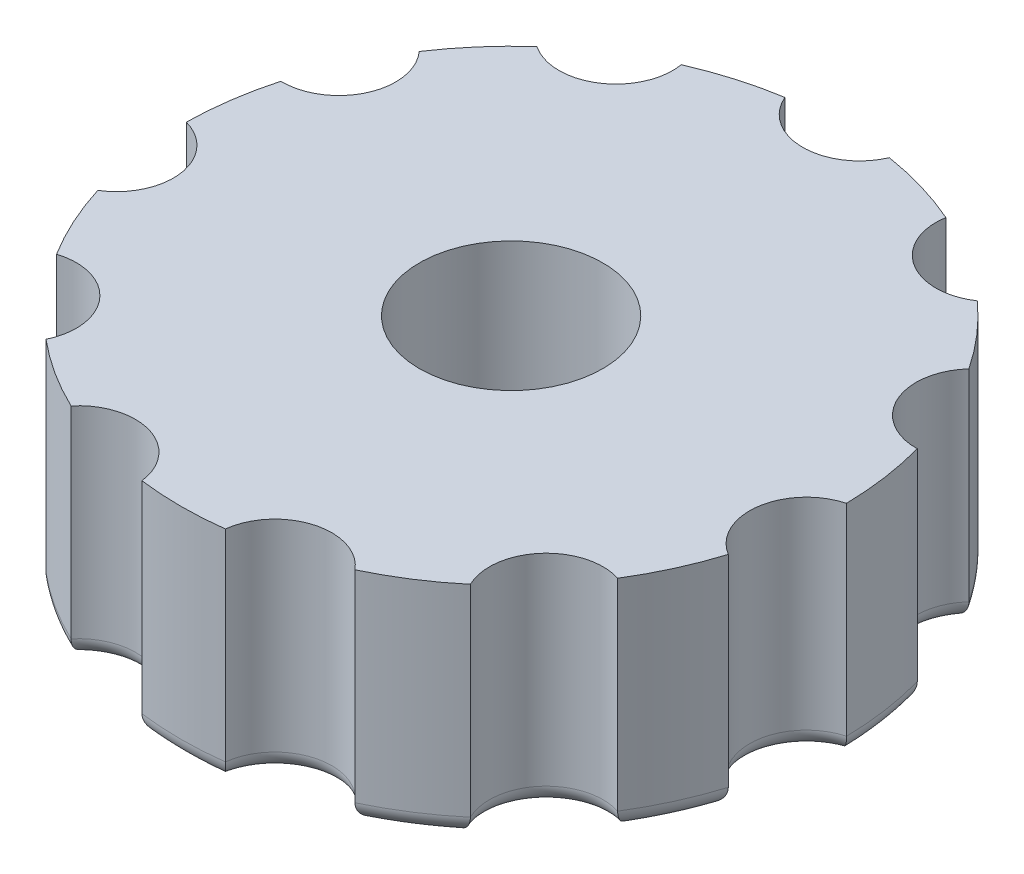
SolidWorks part; units mm, degrees
ref_plane "Front Plane" through (0, 0, 0) normal (0, 0, 1) x (1, 0, 0)
ref_plane "Top Plane" through (0, 0, 0) normal (0, 1, 0) x (1, 0, 0)
ref_plane "Right Plane" through (0, 0, 0) normal (1, 0, 0) x (0, 0, -1)
sketch "Sketch1" plane through (0, 0, 0) normal (0, 1, 0) x (1, 0, 0)
  line L0 (0, 9.5) -> (0, 9) construction
  circle A0 centre (0, 0) radius 9
  circle A1 centre (0, 0) radius 2.5
  circle A2 centre (0, 9.5) radius 1.55
  dimension "D1" = 18
  dimension "D2" = 5
  dimension "D3" = 3.1
  dimension "D4" = 0.5
extrude "Boss-Extrude1" add sketch "Sketch1" along normal blind 6 contours A2 A0 A1 | A0 A2 region at (-5.6744, 0, 6.6557) region at (0, 0, -8.5437)
extrude "Boss-Extrude2" add sketch "Sketch1<3>" along normal blind 2 contours A1
sketch "Sketch1<3>" plane through (0, 0, 0) normal (0, 1, 0) x (1, 0, 0) same geometry as "Sketch1"
ref_axis "Axis1" through (0, 0, 0) along (0, 1, 0)
extrude "Cut-Extrude1" cut sketch "Sketch1<4>" along normal through all contours A2
sketch "Sketch1<4>" plane through (0, 0, 0) normal (0, 1, 0) x (1, 0, 0) same geometry as "Sketch1"
pattern_circular "CirPattern1" count 11 over 360 about axis through (0, 0, 0) along (0, 1, 0) of "Cut-Extrude1"
fillet "Fillet1" radius 0.5 22 edges at (-8.9084, 0, -1.2808) (-7.8691, 0, 1.1314) (-8.1867, 0, 3.7387) (-6.0082, 0, 5.2061) (-4.8658, 0, 7.5713) (-2.2398, 0, 7.628) (0, 0, 9) (2.2398, 0, 7.628) (4.8658, 0, 7.5713) (6.0082, 0, 5.2061) (8.1867, 0, 3.7387) (0, 0, -7.95) (-2.5356, 0, -8.6354) (-4.2981, 0, -6.688) (-6.8017, 0, -5.8937) (-7.2316, 0, -3.3025) (7.8691, 0, 1.1314) (8.9084, 0, -1.2808) (7.2316, 0, -3.3025) (6.8017, 0, -5.8937) (4.2981, 0, -6.688) (2.5356, 0, -8.6354)
